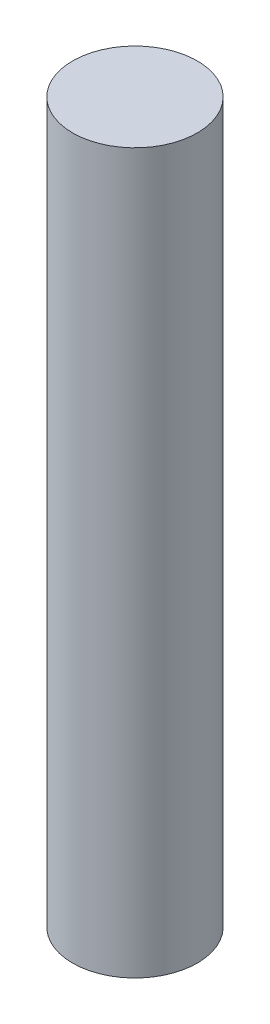
SolidWorks part; units mm, degrees
material "Stainless Steel (ferritic)"
ref_plane "Front Plane" through (0, 0, 0) normal (0, 0, 1) x (1, 0, 0)
ref_plane "Top Plane" through (0, 0, 0) normal (0, 1, 0) x (1, 0, 0)
ref_plane "Right Plane" through (0, 0, 0) normal (1, 0, 0) x (0, 0, -1)
sketch "Sketch1" plane through (0, 0, 0) normal (0, 1, 0) x (1, 0, 0)
  circle A0 centre (0, 0) radius 8.5
  dimension "D1" = 17
extrude "Boss-Extrude1" add sketch "Sketch1" along normal blind 98
ref_plane "Plane1" through (0, 82.02, 0) normal (0, 1, 0) x (1, 0, 0)
sketch "Sketch5" plane through (0, 82.02, 0) normal (0, 1, 0) x (1, 0, 0)
  line L1 (-2, 0) -> (2, 0)
  line L2 (-2, 0) -> (-2, 11.5)
  line L3 (-2, 11.5) -> (2, 11.5)
  line L4 (2, 0) -> (2, 11.5)
  point P4 (0, 0)
  dimension "D1" = 11.5
  dimension "D2" = 4
